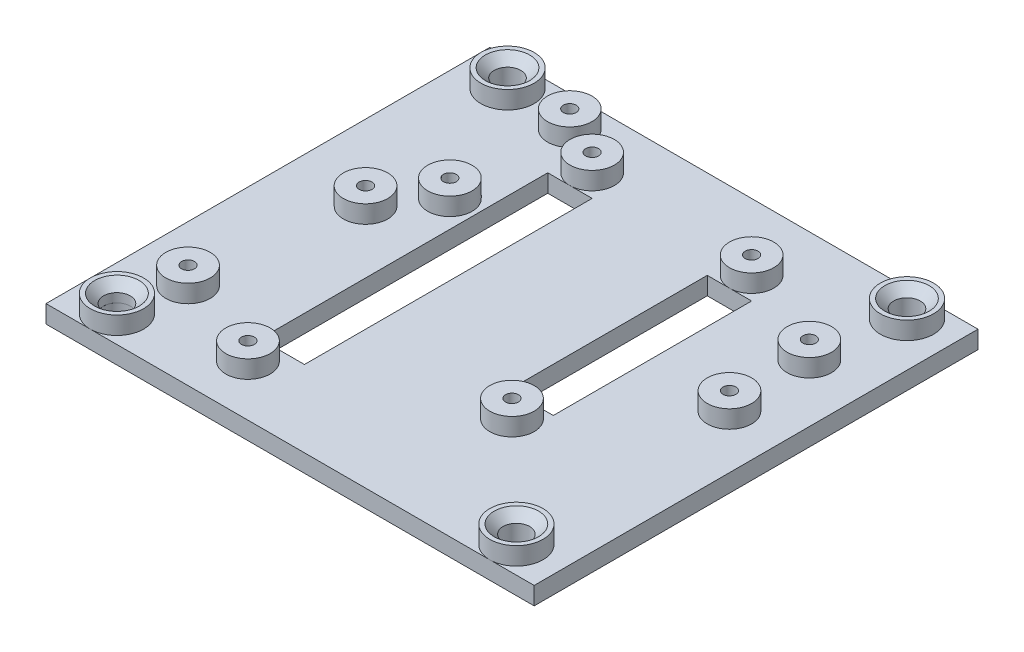
SolidWorks part; units mm, degrees
ref_plane "Спереди" through (0, 0, 0) normal (0, 0, 1) x (1, 0, 0)
ref_plane "Сверху" through (0, 0, 0) normal (0, 1, 0) x (1, 0, 0)
ref_plane "Справа" through (0, 0, 0) normal (1, 0, 0) x (0, 0, -1)
ref_plane "Плоскость4" through (0, 108.9382, 0) normal (0, 1, 0) x (1, 0, 0)
sketch "Эскиз1" plane through (0, 108.9382, 0) normal (0, 1, 0) x (1, 0, 0)
  line L0 (110.2641, -24.3229) -> (110.2641, -124.3229)
  line L1 (110.2641, -24.3229) -> (110.2641, -124.3229) construction
  line L2 (110.2641, -24.3229) -> (110.2641, -38.6516) construction
  line L3 (-15.3081, -124.3229) -> (15.3081, -124.3229) construction
  line L4 (110.2641, -124.3229) -> (0.2823, -124.3229)
  line L5 (0.2823, -124.3229) -> (0.2823, -24.3229)
  line L6 (18.6005, -24.2989) -> (-18.5367, -24.3475) construction
  line L7 (0.2823, -24.3229) -> (110.2641, -24.3229)
  circle A0 centre (10.2641, -30.3229) radius 3
  circle A1 centre (100.2641, -30.3229) radius 3
  circle A2 centre (100.2641, -118.3229) radius 3
  circle A3 centre (10.2641, -118.3229) radius 3
extrude "Бобышка-Вытянуть1" add sketch "Эскиз1" along normal blind 4
ref_plane "Плоскость5" through (0, 112.9382, 0) normal (0, 1, 0) x (1, 0, 0)
sketch "Эскиз2" plane through (0, 112.9382, 0) normal (0, 1, 0) x (1, 0, 0)
  line L0 (31.2823, -42.2757) -> (31.2823, -107.0938)
  line L9 (31.2823, -107.0938) -> (41.2823, -107.0938)
  line L10 (41.2823, -107.0938) -> (41.2823, -42.2757)
  line L11 (41.2823, -42.2757) -> (31.2823, -42.2757)
  line L12 (69.2641, -44.3229) -> (79.2641, -44.3229)
  line L13 (79.2641, -44.3229) -> (79.2641, -89.0117)
  line L14 (79.2641, -89.0117) -> (69.2641, -89.0117)
  line L15 (69.2641, -89.0117) -> (69.2641, -44.3229)
  circle A0 centre (25.2823, -31.3229) radius 1.45
  circle A1 centre (25.2823, -31.3229) radius 5
  circle A2 centre (36.2823, -37.2757) radius 1.45
  circle A3 centre (36.2823, -37.2757) radius 5
  circle A4 centre (17.2823, -69.3229) radius 1.45
  circle A5 centre (17.2823, -69.3229) radius 5
  circle A6 centre (25.2823, -58.3229) radius 1.45
  circle A7 centre (25.2823, -58.3229) radius 5
  circle A8 centre (12.7823, -104.8229) radius 1.45
  circle A9 centre (12.7823, -104.8229) radius 5
  circle A10 centre (34.2823, -112.8229) radius 1.45
  circle A11 centre (34.2823, -112.8229) radius 5
  circle A12 centre (74.2641, -39.3229) radius 1.45
  circle A13 centre (74.2641, -39.3229) radius 5
  circle A14 centre (97.2641, -49.3229) radius 1.45
  circle A15 centre (97.2641, -49.3229) radius 5
  circle A16 centre (98.2641, -68.3229) radius 1.45
  circle A17 centre (98.2641, -68.3229) radius 5
  circle A18 centre (75.2641, -94.3229) radius 1.45
  circle A19 centre (75.2641, -94.3229) radius 5
  circle A20 centre (10.2641, -30.3229) radius 3
  circle A21 centre (10.2641, -30.3229) radius 6
  circle A22 centre (100.2641, -30.3229) radius 3
  circle A23 centre (100.2641, -30.3229) radius 6
  circle A24 centre (100.2641, -118.3229) radius 3
  circle A25 centre (100.2641, -118.3229) radius 6
  circle A26 centre (10.2641, -118.3229) radius 3.0092
  circle A27 centre (10.2641, -118.3229) radius 6
  point P61 (0, 0)
extrude "Бобышка-Вытянуть2" add sketch "Эскиз2" along normal blind 4 contours A21 A20 | A1 A0 | A3 A2 | A13 A12 | A23 A22 | A15 A14 | A17 A16 | A19 A18 | A25 A24 | A11 A10 | A9 A8 | A5 A4 | A7 A6 | A27 A26 region at (32.8467, 112.9382, 33.8402) region at (70.8286, 112.9382, 35.8874) region at (20.4237, 112.9382, 31.3229) region at (12.4237, 112.9382, 69.3229) region at (20.4237, 112.9382, 58.3229) region at (7.9237, 112.9382, 104.8229) region at (29.4237, 112.9382, 112.8229) region at (92.4055, 112.9382, 49.3229) region at (93.4055, 112.9382, 68.3229) region at (70.4055, 112.9382, 94.3229) region at (4.4338, 112.9382, 30.3229) region at (94.4338, 112.9382, 30.3229) region at (94.4338, 112.9382, 118.3229) region at (4.4338, 112.9382, 118.3229)
extrude "Вырез-Вытянуть1" cut sketch "Эскиз2<3>" against normal through all both and the other way through all contours L10 L11 L0 L9 | L15 L14 L13 L12 region at (36.2823, 112.9382, 74.6848) region at (74.2641, 112.9382, 66.6673)
sketch "Эскиз2<3>" plane through (0, 112.9382, 0) normal (0, 1, 0) x (1, 0, 0) same geometry as "Эскиз2"
chamfer "Фаска1" distance 2 angle 45 4 edges at (10.2641, 116.9382, 121.3321) (100.2641, 116.9382, 121.3229) (100.2641, 116.9382, 33.3229) (10.2641, 116.9382, 33.3229)
